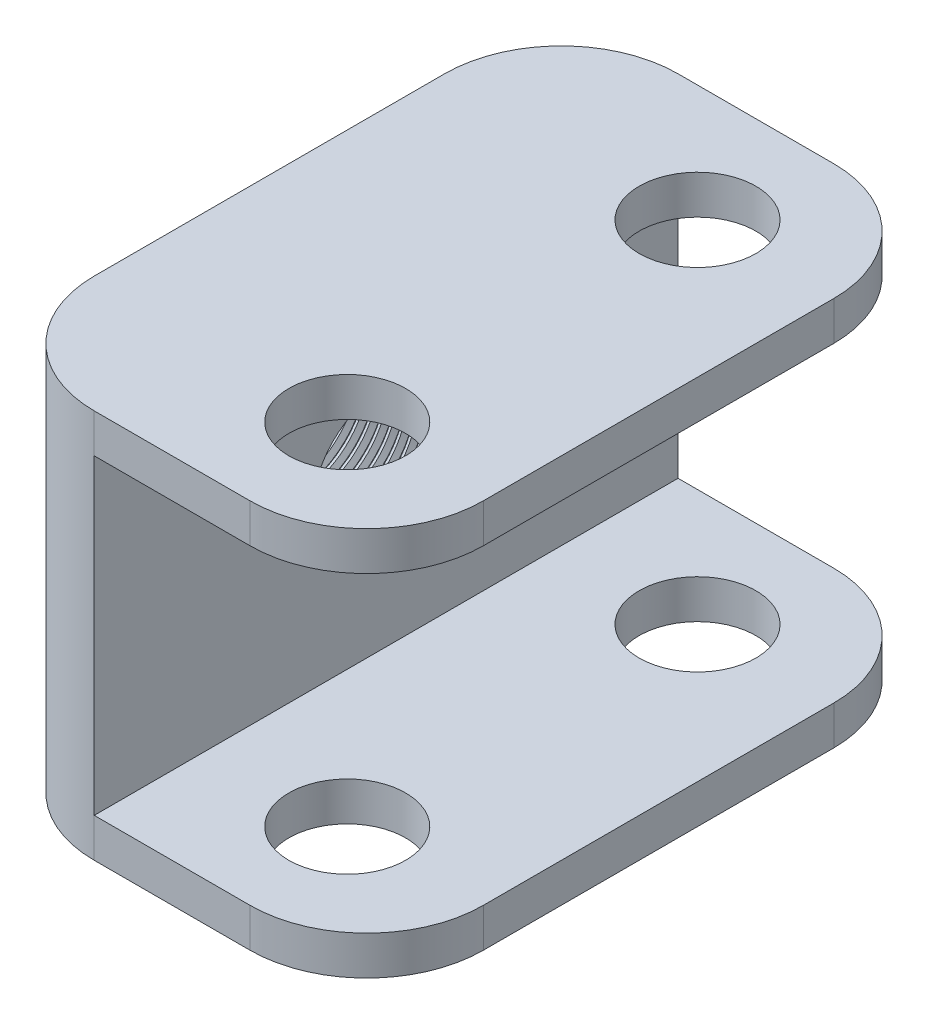
SolidWorks part; units mm, degrees
ref_plane "Front Plane" through (0, 0, 0) normal (0, 0, 1) x (1, 0, 0)
ref_plane "Top Plane" through (0, 0, 0) normal (0, 1, 0) x (1, 0, 0)
ref_plane "Right Plane" through (0, 0, 0) normal (1, 0, 0) x (0, 0, -1)
sketch "Sketch1" plane through (0, 0, 0) normal (0, 0, 1) x (1, 0, 0)
  line L1 (0, 0) -> (30, 0)
  line L2 (0, 0) -> (0, 100)
  line L3 (0, 100) -> (30, 100)
  line L4 (30, 10) -> (30, 90)
  line L5 (30, 100) -> (100, 100)
  line L7 (30, 90) -> (100, 90)
  line L8 (100, 100) -> (100, 90)
  line L9 (100, 0) -> (100, 10)
  line L10 (30, 10) -> (100, 10)
  line L11 (30, 0) -> (100, 0)
  point P8 (0, 0)
  point P9 (0, 0)
  dimension "D1" = 10
  dimension "D2" = 10
  dimension "D3" = 80
  dimension "D4" = 100
  dimension "D5" = 30
  dimension "D6" = 100
extrude "Boss-Extrude1" add sketch "Sketch1" along normal blind 150 contours L2 L3 L5 L8 L7 L4 L10 L9 L11 L1
sketch "Sketch2" plane through (0, 100, 0) normal (0, 1, 0) x (1, 0, 0)
  line L0 (100, -150) -> (100, 0) construction
  circle A0 centre (65, -30) radius 15
  circle A1 centre (65, -120) radius 15
  point P4 (0, 0)
  dimension "D3" = 30
  dimension "D4" = 30
  dimension "D1" = 35
  dimension "D2" = 30
  dimension "D5" = 30
extrude "Cut-Extrude1" cut sketch "Sketch2" against normal blind 150
fillet "Fillet1" radius 30 6 edges at (0, 50, 150) (0, 50, 0) (100, 5, 0) (100, 5, 150) (100, 95, 150) (100, 95, 0)
sketch "Sketch3" plane through (0, 0, 0) normal (-1, 0, 0) x (0, 0, 1)
  line L0 (75, 100) -> (75, 0) construction
  line L1 (120, 100) -> (30, 100) construction
  line L2 (120, 0) -> (30, 0) construction
  circle A0 centre (75, 50) radius 18
  dimension "D1" = 36
extrude "Cut-Extrude2" cut sketch "Sketch3" against normal blind 150
thread "Thread1" pitch 2.5 method cut profile "Thread Profile1" start angle 0, offset 0, length 30, pitch 2.5, diameter 36
ref_plane "Plane1" through (0, 50, 57) normal (0, -1, 0) x (0, 0, -1)
sketch "Thread Profile1" plane through (0, 50, 57) normal (0, -1, 0) x (0, 0, -1)
  line L0 (0, 0) -> (0, 2.5) construction
  line L1 (0, 0) -> (1.3532, 0.7812)
  line L2 (1.3532, 0.7812) -> (1.3532, 1.0937)
  line L3 (1.3532, 1.0937) -> (0, 1.875)
  line L4 (1.3532, 0.9375) -> (0, 0.9375) construction
  line L11 (0, 0) -> (0, 1.875)
  point P2 (0, 0)
  dimension "Pitch" = 2.5
  dimension "Profile_Angle" = 60
  dimension "Profile_Land" = 0.3125
  dimension "Profile_Height" = 1.3532
sketch "Sketch13" plane through (0, 50, 0) normal (0, 1, 0) x (1, 0, 0)
  line L4 (1.0937, -55.6468) -> (0.7812, -55.6468)
  line L5 (0.7812, -55.6468) -> (0, -57)
  line L6 (0, -57) -> (1.875, -57)
  line L7 (1.875, -57) -> (1.0937, -55.6468)
  line L8 (1.0937, -55.6468) -> (0.7812, -55.6468)
  line L9 (0.7812, -55.6468) -> (0, -57)
  line L10 (0, -57) -> (1.875, -57)
  line L11 (1.875, -57) -> (1.0937, -55.6468)
  dimension "D1" = 0
revolve "Cut-Revolve1" cut sketch "Sketch13" angle 360 about axis through (150, 50, 75) along (-1, 0, 0)
